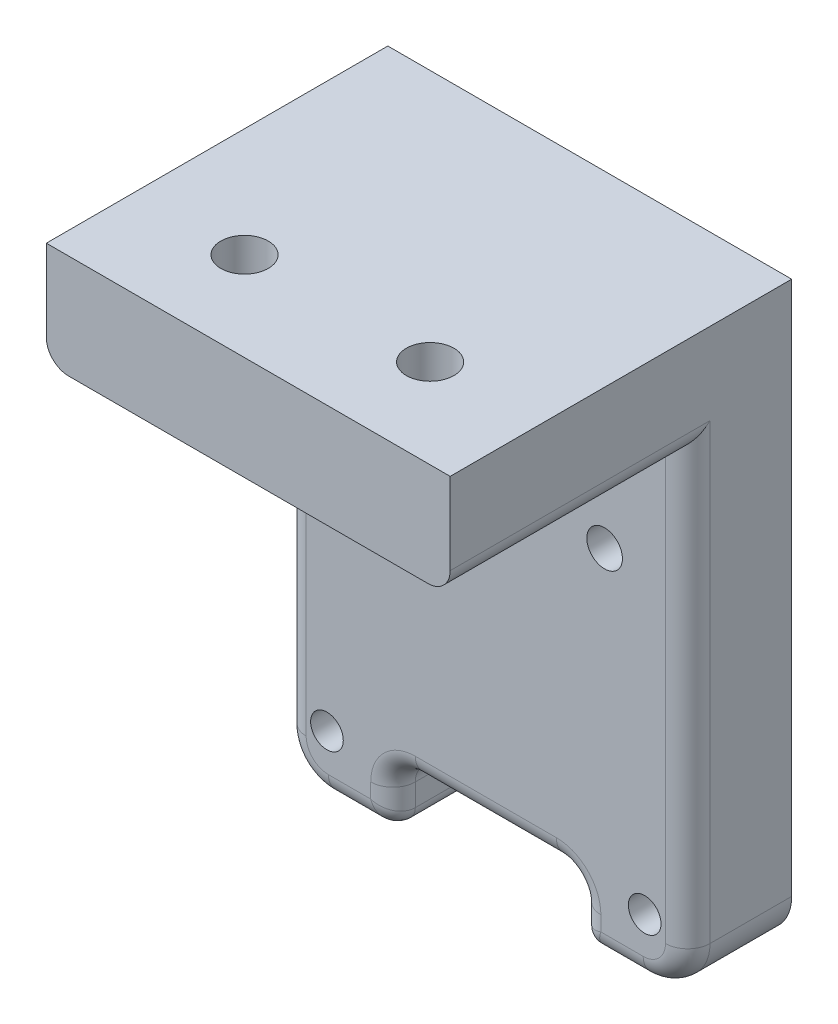
SolidWorks part; units mm, degrees
ref_plane "Front Plane" through (0, 0, 0) normal (0, 0, 1) x (1, 0, 0)
ref_plane "Top Plane" through (0, 0, 0) normal (0, 1, 0) x (1, 0, 0)
ref_plane "Right Plane" through (0, 0, 0) normal (1, 0, 0) x (0, 0, -1)
sketch "Sketch1" plane through (0, 0, 0) normal (0, 0, 1) x (1, 0, 0)
  line L0 (-10.7, 0) -> (10.7, 0) construction
  line L1 (-13.6, 4) -> (-13.6, 28)
  line L6 (-13.6, 4) -> (13.6, 4) construction
  line L7 (-13.6, 4) -> (-13.6, -1)
  line L12 (-10.6, -4) -> (-7.25, -4)
  line L13 (13.6, 4) -> (13.6, -1)
  line L14 (-13.6, 4) -> (13.6, -4) construction
  line L15 (-13.6, -4) -> (13.6, 4) construction
  line L16 (-13.6, 28) -> (13.6, 28)
  line L17 (13.6, 28) -> (13.6, 4)
  line L18 (-6.25, -3) -> (-6.25, -1.5)
  line L19 (-4.75, 0) -> (4.75, 0)
  line L20 (6.25, -1.5) -> (6.25, -3)
  line L21 (7.25, -4) -> (10.6, -4)
  circle A0 centre (-10.7, 0) radius 1.1
  circle A1 centre (10.7, 0) radius 1.1
  arc A2 (10.6, -4) -> (13.6, -1) centre (10.6, -1) ccw
  arc A3 (-13.6, -1) -> (-10.6, -4) centre (-10.6, -1) ccw
  arc A4 (4.75, 0) -> (6.25, -1.5) centre (4.75, -1.5) cw
  arc A5 (-6.25, -1.5) -> (-4.75, 0) centre (-4.75, -1.5) cw
  arc A6 (6.25, -3) -> (7.25, -4) centre (7.25, -3) ccw
  arc A7 (-6.25, -3) -> (-7.25, -4) centre (-7.25, -3) cw
  point P4 (0, 0)
  point P7 (0, 1.4865)
  point P8 (0, 0)
  point P13 (0, -1.35)
  point P25 (0, 0)
  point P29 (6.25, 0)
  point P32 (-6.25, 0)
  point P35 (6.25, -4)
  dimension "D2" = 2.2
  dimension "D7" = 12.5
  dimension "D5" = 3
  dimension "D8" = 1.5
  dimension "D9" = 1
  dimension "D1" = 21.4
  dimension "D3" = 27.2
  dimension "D4" = 8
  dimension "D6" = 28
extrude "Boss-Extrude1" add sketch "Sketch1" along normal blind 7
sketch "Sketch2" plane through (0, 0, 0) normal (0, 0, 1) x (1, 0, 0)
  line L0 (13.6, 28) -> (-13.6, 28) construction
  line L1 (13.6, 28) -> (-13.6, 28)
  line L2 (-13.6, 28) -> (-13.6, 35)
  line L3 (-13.6, 35) -> (13.6, 35)
  line L4 (13.6, 35) -> (13.6, 28)
  dimension "D1" = 7
extrude "Boss-Extrude2" add sketch "Sketch2" along normal blind 23
sketch "Sketch4" plane through (0, 35, 0) normal (0, 1, 0) x (1, 0, 0)
  line L0 (6.25, -17) -> (-6.25, -17) construction
  line L1 (13.6, 0) -> (-13.6, 0) construction
  circle A0 centre (6.25, -17) radius 1.6
  circle A1 centre (-6.25, -17) radius 1.6
  point P7 (0, -17)
  dimension "D2" = 3.2
  dimension "D1" = 17
  dimension "D3" = 12.5
extrude "Cut-Extrude1" cut sketch "Sketch4" against normal up to next
sketch "Sketch5" plane through (0, 21, 7) normal (0, 0, 1) x (1, 0, 0)
  line L0 (8, -1) -> (-8, -1) construction
  line L2 (13.6, 7) -> (-13.6, 7) construction
  circle A0 centre (-8, -1) radius 1.2
  circle A1 centre (8, -1) radius 1.2
  point P7 (0, -1)
  dimension "D2" = 2.4
  dimension "D1" = 16
  dimension "D3" = 8
extrude "Cut-Extrude2" cut sketch "Sketch5" against normal up to next
fillet "Fillet1" radius 1.5 15 edges at (13.6, 13.5, 7) (-8.925, -4, 7) (-13.6, 13.5, 7) (-13.6, 28, 15) (13.6, 28, 15) (12.7213, -3.1213, 7) (-12.7213, -3.1213, 7) (8.925, -4, 7) (6.5429, -3.7071, 7) (6.25, -2.25, 7) (5.8107, -0.4393, 7) (0, 0, 7) (-5.8107, -0.4393, 7) (-6.25, -2.25, 7) (-6.5429, -3.7071, 7)
